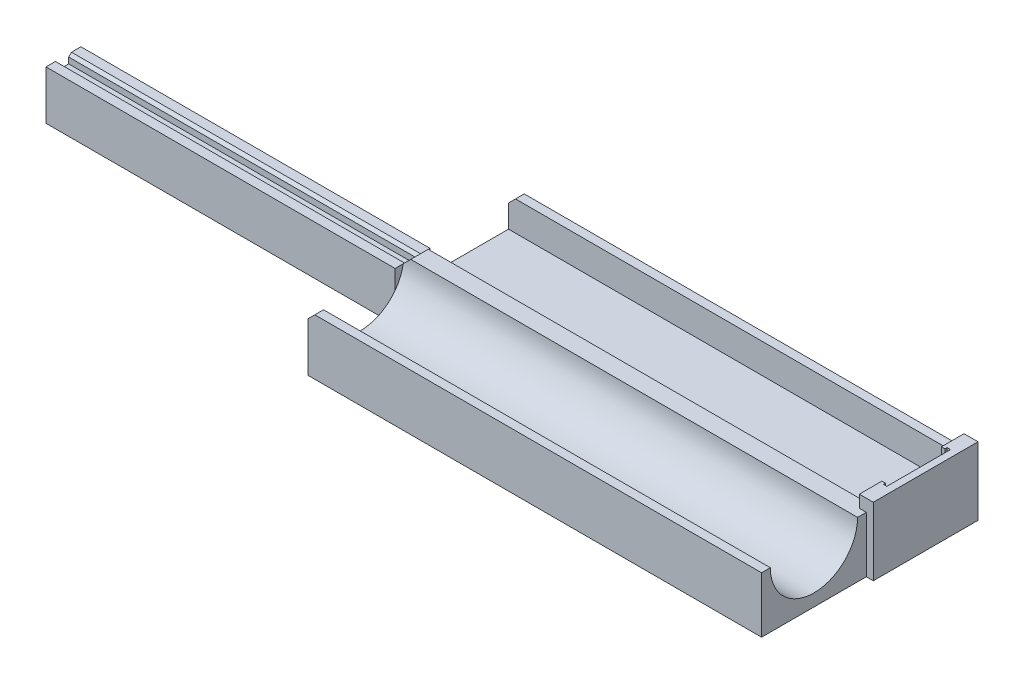
SolidWorks part; units mm, degrees
ref_plane "Front Plane" through (0, 0, 0) normal (0, 0, 1) x (1, 0, 0)
ref_plane "Top Plane" through (0, 0, 0) normal (0, 1, 0) x (1, 0, 0)
ref_plane "Right Plane" through (0, 0, 0) normal (1, 0, 0) x (0, 0, -1)
sketch "Sketch1" plane through (0, 0, 0) normal (0, 1, 0) x (1, 0, 0)
  line L1 (-65, 30) -> (65, 30)
  line L2 (-65, 30) -> (-65, -30)
  line L3 (-65, -30) -> (65, -30)
  line L4 (65, 30) -> (65, -30)
  line L5 (-65, 30) -> (65, -30) construction
  line L6 (-65, -30) -> (65, 30) construction
  point P0 (0, 0)
  dimension "D1" = 130
  dimension "D2" = 60
extrude "Boss-Extrude1" add sketch "Sketch1" along normal blind 16
sketch "Sketch2" plane through (65, 0, 0) normal (1, 0, 0) x (0, 0, -1)
  line L0 (0, 16) -> (-30, 16)
  line L1 (-30, 16) -> (30, 16) construction
  circle A0 centre (-15, 16) radius 19.32
  circle A1 centre (-15, 16) radius 12.5
  line M3 (30, 16) -> (-30, 16)
  dimension "D1" = 38.64
  dimension "D2" = 25
extrude "Cut-Extrude1" cut sketch "Sketch2" against normal through all contours A1 M3 region at (65, 10.6948, 15)
sketch "Sketch3" plane through (65, 0, 0) normal (1, 0, 0) x (0, 0, -1)
  line L0 (30, 0) -> (-30, 0)
  line L1 (0, 0) -> (0, 16)
  line L2 (-2.5, 16) -> (30, 16) construction
  line L3 (0, 16) -> (30, 16)
  line L4 (15, 16) -> (15, 0) construction
  line L5 (23.525, 19.5) -> (23.525, 10.5)
  line L6 (5.875, 19.5) -> (24.125, 19.5)
  line L7 (5.875, 19.5) -> (5.875, 10.5)
  line L8 (5.875, 10.5) -> (24.125, 10.5)
  line L9 (24.125, 19.5) -> (24.125, 10.5)
  line L10 (5.875, 19.5) -> (24.125, 10.5) construction
  line L11 (5.875, 10.5) -> (24.125, 19.5) construction
  line L12 (24.125, 11.1) -> (5.875, 11.1)
  line L13 (6.475, 10.5) -> (6.475, 19.5)
  line L14 (30, 0) -> (30, 16)
  line L15 (0, 16) -> (0, 19.5)
  line L16 (0, 19.5) -> (5.875, 19.5)
  line L17 (24.125, 19.5) -> (30, 19.5)
  line L18 (30, 19.5) -> (30, 16)
  point P13 (15, 15)
  line M8 (30, 16) -> (-2.5, 16)
  line M13 (30, 0) -> (30, 16)
  dimension "D1" = 18.25
  dimension "D2" = 9
  dimension "D3" = 0.6
  dimension "D4" = 0.6
  dimension "D5" = 0.6
  dimension "D6" = 1
extrude "Cut-Extrude2" cut sketch "Sketch3" against normal blind 2 contours L13 L3 L5 L6 | L13 L12 L5 L3 | L8 L9 L6 L7 region at (65, 13.55, -15) region at (65, 17.75, -15)
extrude "Boss-Extrude2" add sketch "Sketch3<7>" along normal blind 1 from surface contours L12 L9 L3 L5 | L9 L6 L5 L3 | L13 L6 L7 M8 | L12 L13 L7 M8 region at (65, 13.55, -23.825) region at (65, 17.75, -23.825) region at (65, 17.75, -6.175) region at (65, 13.55, -6.175) starting at face at (63, 13.25, -15)
sketch "Sketch3<7>" plane through (65, 0, 0) normal (1, 0, 0) x (0, 0, -1) same geometry as "Sketch3"
extrude "Boss-Extrude3" add sketch "Sketch3<9>" along normal blind 2 contours L16 L15 L7 M8 | L9 L8 L7 L1 L0 M8 M13 | L12 L13 L7 M8 | L13 L12 L5 L3 | L13 L6 L7 M8 | L13 L3 L5 L6 | L13 L8 L5 L12 | L8 L13 L12 L7 | L12 L9 L3 L5 | L9 L12 L5 L8 | L9 L6 L5 L3 | L18 L17 L9 M8 region at (65, 6.6119, -15) region at (65, 17.75, -27.0625) region at (65, 17.75, -2.9375) region at (65, 13.55, -23.825) region at (65, 17.75, -23.825) region at (65, 17.75, -6.175) region at (65, 13.55, -6.175) region at (65, 13.55, -15) region at (65, 17.75, -15) region at (65, 10.8, -23.825) region at (65, 10.8, -6.175) region at (65, 10.8, -15)
sketch "Sketch3<9>" plane through (65, 0, 0) normal (1, 0, 0) x (0, 0, -1) same geometry as "Sketch3"
extrude "Boss-Extrude4" add sketch "Sketch3<10>" against normal blind 2 contours L16 L15 L7 M8 | L18 L17 L9 M8 region at (65, 17.75, -27.0625) region at (65, 17.75, -2.9375)
sketch "Sketch3<10>" plane through (65, 0, 0) normal (1, 0, 0) x (0, 0, -1) same geometry as "Sketch3"
sketch "Sketch4" plane through (-65, 0, 0) normal (-1, 0, 0) x (0, 0, 1)
  line L0 (0, 0) -> (0, 16)
  line L1 (-30, 16) -> (2.5, 16) construction
  line L2 (0, 0) -> (-30, 0) construction
  line L3 (-2.5, 22.5) -> (-27.5, 22.5)
  line L4 (-2.5, 22.5) -> (-2.5, 7.5)
  line L5 (-2.5, 7.5) -> (-27.5, 7.5)
  line L6 (-27.5, 22.5) -> (-27.5, 7.5)
  line L7 (-2.5, 22.5) -> (-27.5, 7.5) construction
  line L8 (-2.5, 7.5) -> (-27.5, 22.5) construction
  line L9 (-15, 0) -> (-15, 39.4252) construction
  point P5 (-15, 15)
  point P14 (0, 0)
  line M7 (2.5, 16) -> (-30, 16)
  dimension "D1" = 25
  dimension "D2" = 15
  dimension "D3" = 15
extrude "Cut-Extrude3" cut sketch "Sketch4" against normal up to surface (128 mm away) contours L6 L5 L4 M7 | L3 L6 L4 M7 region at (-65, 19.25, -15) region at (-65, 11.75, -15) up to face at (63, 17.75, -3.2375)
sketch "Sketch5" plane through (-65, 0, 0) normal (-1, 0, 0) x (0, 0, 1)
  line L0 (-27.5, 16) -> (-27.5, 7.5) construction
  line L1 (-2.5, 7.5) -> (-27.5, 7.5) construction
  line L2 (-2.5, 7.5) -> (-2.5, 24.5) construction
  line L3 (-2.5, 24.5) -> (-27.5, 24.5) construction
  line L4 (-27.5, 7.5) -> (-27.5, 24.5) construction
  line L5 (-2.5, 7.5) -> (-27.5, 24.5) construction
  line L6 (-2.5, 24.5) -> (-27.5, 7.5) construction
  line L7 (15, 16) -> (-15, 16) construction
  line L8 (-30, 0) -> (30, 0) construction
  line L9 (1.5, 14) -> (1.5, 11.5)
  line L10 (-5, 0) -> (5, 0)
  line L11 (-5, 0) -> (-5, 14)
  line L12 (-5, 14) -> (-1.5, 14)
  line L13 (5, 0) -> (5, 14)
  line L14 (-5, 0) -> (5, 14) construction
  line L15 (-5, 14) -> (5, 0) construction
  line L16 (1.5, 11.5) -> (-1.5, 11.5)
  line L17 (-1.5, 11.5) -> (-1.5, 14)
  line L18 (0, 0) -> (0, 11.5) construction
  line L19 (1.5, 14) -> (5, 14)
  circle A0 centre (15, 16) radius 12.5 construction
  arc A1 (2.5, 16) -> (27.5, 16) centre (15, 16) ccw construction
  point P6 (-15, 16)
  point P10 (0, 0)
  point P21 (0, 7)
  point P30 (0, 11.5)
  line M15 (-2.5, 7.5) -> (-27.5, 7.5)
  line M19 (-30, 0) -> (30, 0)
  arc M22 (27.5, 16) -> (2.5, 16) centre (15, 16) cw
  line M24 (-2.5, 16) -> (-2.5, 7.5)
  dimension "D1" = 14
  dimension "D2" = 10
  dimension "D3" = 3
  dimension "D4" = 2.5
extrude "Boss-Extrude10" add sketch "Sketch5" along normal blind 100 contours L19 L9 L16 L17 L12 L11 L13 M24 M15 M19 M22 | L12 L11 M15 M24 | L19 L13 M22 | L11 L12 L17 L16 L9 L19 L13 L10 region at (-65, 5.677, 0.2624) region at (-65, 11.9877, 4.1241) region at (-65, 10.75, -3.75)
chamfer "Chamfer1" distance 0.8 angle 45 2 edges at (-115, 14, 1.5) (-115, 14, -1.5)
chamfer "Chamfer2" distance 2 angle 45 3 edges at (-65, 16, -28.75) (-65, 16, 28.75) (-65, 16, 0)
